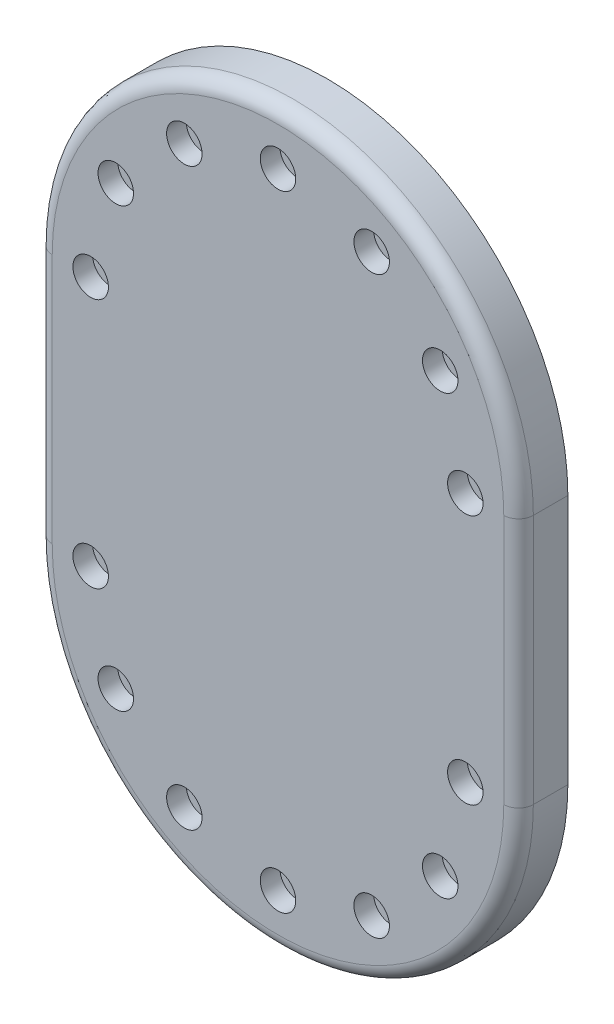
SolidWorks part; units mm, degrees
note: The reader was unsure of these and kept them because the rebuilt part matched: shared geometry of "Sketch1<3>".
ref_plane "Front Plane" through (0, 0, 0) normal (0, 0, 1) x (1, 0, 0)
ref_plane "Top Plane" through (0, 0, 0) normal (0, 1, 0) x (1, 0, 0)
ref_plane "Right Plane" through (0, 0, 0) normal (1, 0, 0) x (0, 0, -1)
sketch "Sketch1" plane through (0, 0, 0) normal (0, 0, 1) x (1, 0, 0)
  line L0 (0, 31.75) -> (0, -31.75) construction
  line L1 (61, 31.75) -> (61, -31.75)
  line L2 (-61, 31.75) -> (-61, -31.75)
  line L3 (0, 31.75) -> (0, -31.75) construction
  line L4 (11.5, 31.75) -> (11.5, -31.75)
  line L5 (-11.5, 31.75) -> (-11.5, -31.75)
  arc A0 (61, 31.75) -> (-61, 31.75) centre (0, 31.75) ccw
  arc A1 (-61, -31.75) -> (61, -31.75) centre (0, -31.75) ccw
  arc A2 (11.5, 31.75) -> (-11.5, 31.75) centre (0, 31.75) ccw
  arc A3 (-11.5, -31.75) -> (11.5, -31.75) centre (0, -31.75) ccw
  point P2 (0, 0)
  point P9 (0, 0)
  point P15 (0, 0)
  dimension "D3" = 11.5
  dimension "D1" = 63.5
  dimension "D2" = 122
extrude "Boss-Extrude1" add sketch "Sketch1" along normal blind 12.5 contours L2 A1 L1 A0
extrude "Cut-Extrude1" cut sketch "Sketch1<3>" along normal blind 6.25 contours L5 A3 L4 A2
sketch "Sketch1<3>" plane through (0, 0, 0) normal (0, 0, 1) x (1, 0, 0) same geometry as "Sketch1"
fillet "Fillet1" radius 1.75 4 edges at (11.5, 0, 0) (0, -43.25, 0) (-11.5, 0, 0) (0, 43.25, 0)
fillet "Fillet2" radius 3.75 4 edges at (61, 0, 12.5) (0, -92.75, 12.5) (-61, 0, 12.5) (0, 92.75, 12.5)
hole_wizard "Hole1" positions "Sketch2" profile "Sketch3" legacy
sketch "Sketch2" plane through (0, 0, 12.5) normal (0, 0, 1) x (1, 0, 0)
  point P0 (-47.5, 31.75)
  point P4 (0, 0)
  point P5 (0, 0)
  point P7 (0, 0)
  dimension "D1" = 47.5
sketch "Sketch3" plane through (-47.5, 31.75, 12.5) normal (1, 0, 0) x (0, -1, 0)
  line L0 (0, 0) -> (0, 30)
  line L1 (0, 30) -> (2.5, 30)
  line L2 (2.5, 30) -> (2.5, 5)
  line L3 (2.5, 5) -> (4.5, 5)
  line L4 (4.5, 5) -> (4.5, 0)
  line L5 (4.5, 0) -> (0, 0)
  line L6 (0, 110) -> (0, -10) construction
  dimension "Diameter" = 5
  dimension "Depth" = 30
  dimension "C-Bore Diameter" = 9
  dimension "C-Bore Depth" = 5
pattern_circular "CirPattern1" count 7 over 180 about axis through (0, 31.75, 0) along (0, 0, 1) of "Hole1"
mirror "Mirror1" about plane through (0, 0, 0) normal (0, 1, 0) of "CirPattern1", "Hole1"
